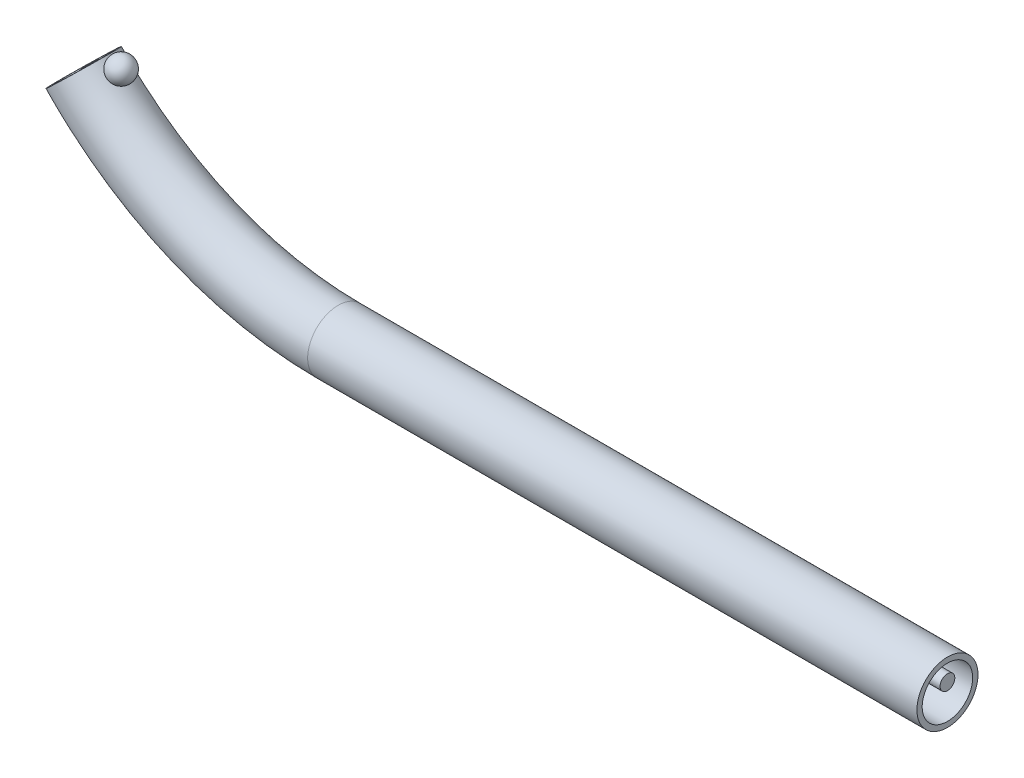
SolidWorks part; units mm, degrees
ref_plane "Front Plane" through (0, 0, 0) normal (0, 0, 1) x (1, 0, 0)
ref_plane "Top Plane" through (0, 0, 0) normal (0, 1, 0) x (1, 0, 0)
ref_plane "Right Plane" through (0, 0, 0) normal (1, 0, 0) x (0, 0, -1)
ref_axis "Axis1" through (-88.99, 0, 0) along (1, 0, 0)
sketch "Sketch4" plane through (0, 0, 0) normal (0, 0, 1) x (1, 0, 0)
  line L0 (-218.053, 283.5718) -> (61.923, 683.419) construction
  line L1 (-68.365, 0) -> (-65.9542, 0)
  arc A0 (-68.365, 0) -> (-73.5499, 2.2253) centre (-68.365, 7.1532) cw
  point P2 (-73.5499, 2.2253)
  point P3 (-68.365, 0)
sketch "Sketch1" plane through (0, 0, 0) normal (1, 0, 0) x (0, 0, -1)
  circle A0 centre (0, 0) radius 0.61
  circle A1 centre (0, 0) radius 0.39
  dimension "D1" = 1.22
  dimension "D2" = 0.22
extrude "Boss-Extrude1" [suppressed] add sketch "Sketch1" along normal blind 10
ref_plane "Plane1" through (-65.9542, 0, 0) normal (1, 0, 0) x (0, 0, -1)
sketch "Sketch5" plane through (-65.9542, 0, 0) normal (1, 0, 0) x (0, 0, -1)
  circle A0 centre (0, 0) radius 0.6223
  circle A1 centre (0, 0) radius 0.5143
  dimension "D1" = 1.2446
  dimension "D2" = 1.0287
sweep "Sweep2" add profiles "Sketch5" path "Sketch4"
extrude "Boss-Extrude2" add sketch "Sketch5<2>" along normal blind 10
sketch "Sketch5<2>" plane through (-65.9542, 0, 0) normal (1, 0, 0) x (0, 0, -1) same geometry as "Sketch5"
sketch "Sketch6" plane through (0, 0, 0) normal (0, 0, 1) x (1, 0, 0)
  line L0 (-72.7874, 2.8286) -> (-72.7874, 2.3286) construction
  line L1 (-72.9491, 2.3879) -> (-72.6257, 2.7693)
  circle A0 centre (-72.7874, 2.5786) radius 0.25 construction
  arc A1 (-72.9491, 2.3879) -> (-72.6257, 2.7693) centre (-72.7874, 2.5786) ccw
  dimension "D1" = 0.5
revolve "Revolve2" add sketch "Sketch6" angle 360 about L1
sketch "Sketch7" plane through (0, 0, 0) normal (0, 0, 1) x (1, 0, 0)
  line L0 (-68.365, -0.6223) -> (-55.9542, -0.6223) construction
  line L1 (-68.365, -0.6223) -> (-55.9542, -0.6223) construction
  line L2 (-68.365, 0.1777) -> (-55.9542, 0.1777)
  arc A1 (-74.001, 1.7966) -> (-68.365, -0.6223) centre (-68.365, 7.1532) ccw construction
  arc A2 (-74.001, 1.7966) -> (-68.365, -0.6223) centre (-68.365, 7.1532) ccw construction
  arc A3 (-73.4211, 2.3477) -> (-68.365, 0.1777) centre (-68.365, 7.1532) ccw
  dimension "D1" = 0.8
sketch "Sketch8" plane through (-36.0182, 37.8966, 0) normal (-0.6889, 0.7248, 0) x (0.7248, 0.6889, 0)
  circle A0 centre (-51.6014, 0) radius 0.15
  point P0 (-51.6014, 0)
  dimension "D1" = 0.3
sweep "Sweep3" add profiles "Sketch8" path "Sketch7"
